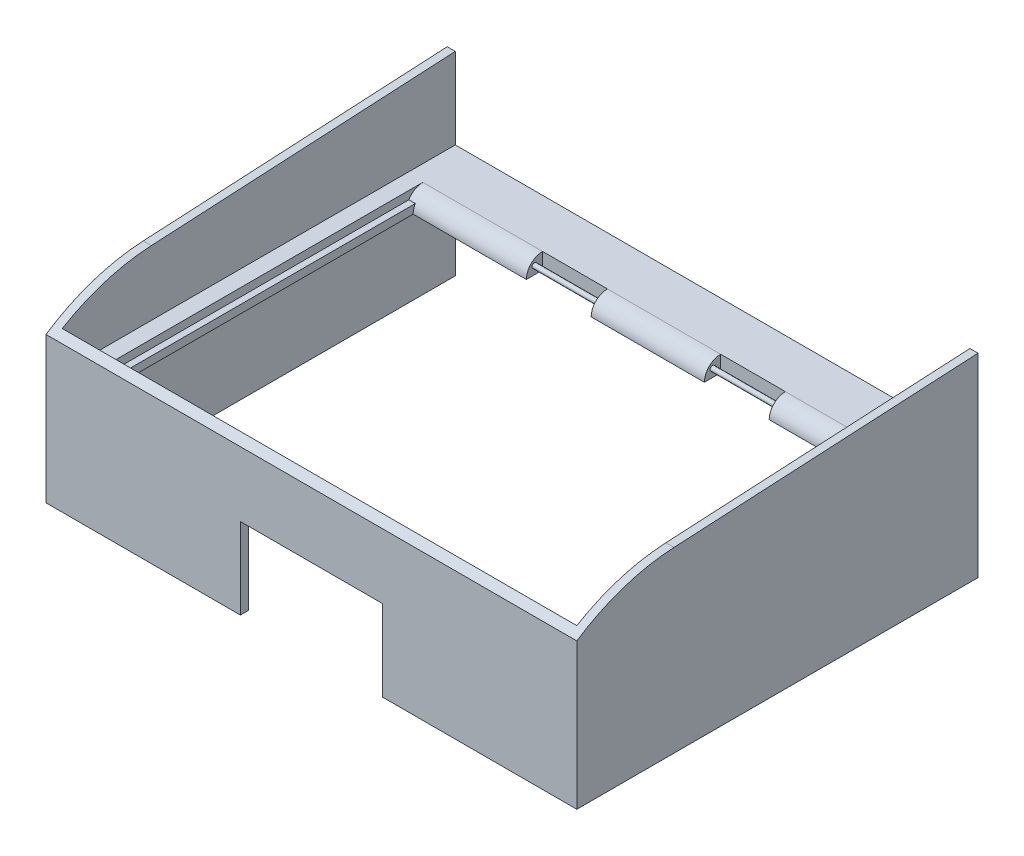
SolidWorks part; units mm, degrees
material "Custom Plastic"
ref_plane "Front Plane" through (0, 0, 0) normal (0, 0, 1) x (1, 0, 0)
ref_plane "Top Plane" through (0, 0, 0) normal (0, 1, 0) x (1, 0, 0)
ref_plane "Right Plane" through (0, 0, 0) normal (1, 0, 0) x (0, 0, -1)
sketch "Sketch1" plane through (0, 0, 0) normal (0, 1, 0) x (1, 0, 0)
  line L15 (-167.513, -142.113) -> (248.567, -142.113)
  line L16 (-167.513, -142.113) -> (-167.513, 172.367)
  line L17 (-167.513, 172.367) -> (248.567, 172.367)
  line L18 (248.567, -142.113) -> (248.567, 172.367)
extrude "Boss-Extrude2" add sketch "Sketch1" along normal blind 152.4
sketch "Sketch2" plane through (0, 152.4, 0) normal (0, 1, 0) x (1, 0, 0)
  line L0 (-167.513, -142.113) -> (248.567, -142.113) construction
  line L1 (-161.163, -135.763) -> (242.217, -135.763)
  line L2 (-161.163, -135.763) -> (-161.163, 172.367)
  line L3 (-161.163, 172.367) -> (242.217, 172.367)
  line L4 (242.217, -135.763) -> (242.217, 172.367)
  line L5 (-167.513, 172.367) -> (-167.513, -142.113) construction
  line L6 (248.567, -142.113) -> (248.567, 172.367) construction
  line L7 (248.567, 172.367) -> (-167.513, 172.367) construction
  dimension "D1" = 6.35
  dimension "D2" = 6.35
  dimension "D3" = 6.35
  dimension "D4" = 0
extrude "Cut-Extrude1" cut sketch "Sketch2" against normal through all
sketch "Sketch3" plane through (248.567, 0, 0) normal (1, 0, 0) x (0, 0, -1)
  line L5 (-142.113, 114.3) -> (-142.113, 152.4)
  line L6 (-142.113, 152.4) -> (-142.113, 0) construction
  line L7 (-142.113, 152.4) -> (172.367, 152.4)
  line L8 (172.367, 152.4) -> (-65.913, 139.7)
  arc A1 (-65.913, 139.7) -> (-142.113, 114.3) centre (-57.8558, -11.4717) ccw
  dimension "D1" = 38.1
  dimension "D2" = 12.7
  dimension "D3" = 76.2
extrude "Cut-Extrude2" cut sketch "Sketch3" against normal through all contours L5 L7 L8 A1
sketch "Sketch4" plane through (0, 0, 142.113) normal (0, 0, 1) x (1, 0, 0)
  line L0 (-167.513, 0) -> (248.567, 0) construction
  line L1 (96.167, 0) -> (-15.113, 0)
  line L2 (96.167, 0) -> (96.167, 63.5)
  line L3 (96.167, 63.5) -> (-15.113, 63.5)
  line L4 (-15.113, 0) -> (-15.113, 63.5)
  line L6 (248.567, 114.3) -> (248.567, 0) construction
  line L7 (-167.513, 114.3) -> (-167.513, 0) construction
  dimension "D1" = 152.4
  dimension "D2" = 152.4
  dimension "D3" = 63.5
extrude "Cut-Extrude3" cut sketch "Sketch4" against normal up to next
sketch "Sketch5" plane through (0, 0, 135.763) normal (0, 0, -1) x (-1, 0, 0)
  line L0 (161.163, 0) -> (161.163, 152.4) construction
  line L1 (-242.217, 88.9) -> (161.163, 88.9)
  line L2 (-242.217, 88.9) -> (-242.217, 76.2)
  line L3 (-242.217, 76.2) -> (161.163, 76.2)
  line L4 (161.163, 88.9) -> (161.163, 76.2)
  line L5 (-96.167, 63.5) -> (15.113, 63.5) construction
  dimension "D1" = 12.7
  dimension "D2" = 12.7
extrude "Boss-Extrude3" add sketch "Sketch5" along normal up to surface (308.13 mm away)
sketch "Sketch6" plane through (0, 88.9, 0) normal (0, 1, 0) x (1, 0, 0)
  line L0 (40.527, -135.763) -> (40.527, 170.2331) construction
  line L1 (242.217, -135.763) -> (-161.163, -135.763) construction
  line L2 (-161.163, 18.302) -> (242.217, 18.302) construction
  line L3 (-161.163, 172.367) -> (-161.163, -135.763) construction
  line L4 (242.217, 172.367) -> (242.217, -135.763) construction
  line L5 (-161.163, 172.367) -> (242.217, 172.367) construction
  line L6 (229.517, -110.363) -> (-148.463, -110.363)
  line L7 (229.517, -110.363) -> (229.517, 121.567)
  line L8 (229.517, 121.567) -> (-148.463, 121.567)
  line L9 (-148.463, -110.363) -> (-148.463, 121.567)
  line L10 (229.517, -110.363) -> (-148.463, 121.567) construction
  line L11 (229.517, 121.567) -> (-148.463, -110.363) construction
  point P10 (40.527, 5.602)
  dimension "D1" = 25.4
  dimension "D2" = 12.7
  dimension "D3" = 50.8
extrude "Cut-Extrude4" cut sketch "Sketch6" against normal blind 6.35
sketch "Sketch7" plane through (0, 82.55, 0) normal (0, 1, 0) x (1, 0, 0)
  line L0 (40.527, -110.363) -> (40.527, 121.567) construction
  line L1 (-148.463, -110.363) -> (229.517, -110.363) construction
  line L2 (229.517, 121.567) -> (-148.463, 121.567) construction
  line L3 (-148.463, 5.602) -> (229.517, 5.602) construction
  line L4 (-148.463, 121.567) -> (-148.463, -110.363) construction
  line L5 (229.517, -110.363) -> (229.517, 121.567) construction
  line L6 (-54.643, 134.267) -> (-3.843, 134.267)
  line L7 (224.437, -105.283) -> (-143.383, -105.283)
  line L8 (224.437, -105.283) -> (224.437, 121.567)
  line L10 (-143.383, -105.283) -> (-143.383, 121.567)
  line L11 (224.437, -105.283) -> (-143.383, 121.567) construction
  line L12 (224.437, 121.567) -> (-143.383, -105.283) construction
  line L13 (-3.843, 134.267) -> (-3.843, 121.567)
  line L14 (-54.643, 134.267) -> (-54.643, 121.567)
  line L15 (-143.383, 121.567) -> (-54.643, 121.567)
  line L16 (224.437, 121.567) -> (135.697, 121.567)
  line L17 (-3.843, 121.567) -> (84.897, 121.567)
  line L18 (40.527, -105.283) -> (-143.383, -105.283) construction
  line L19 (135.697, 134.267) -> (135.697, 121.567)
  line L20 (135.697, 134.267) -> (84.897, 134.267)
  line L21 (84.897, 134.267) -> (84.897, 121.567)
  point P12 (40.527, 8.142)
  point P22 (40.527, 121.567)
  dimension "D1" = 5.08
  dimension "D2" = 5.08
  dimension "D3" = 12.7
  dimension "D4" = 50.8
extrude "Cut-Extrude5" cut sketch "Sketch7" against normal through all both and the other way through all
fillet "Fillet2" radius 12.7 3 edges at (182.607, 88.9, -121.567) (40.527, 88.9, -121.567) (-101.553, 88.9, -121.567)
sketch "Sketch8" plane through (-54.643, 0, 0) normal (1, 0, 0) x (0, 0, -1)
  line L0 (134.267, 82.55) -> (88.213, 82.55) construction
  line L1 (134.267, 76.2) -> (134.267, 88.9) construction
  line L2 (127.917, 76.2) -> (127.917, 94.6214) construction
  line L3 (134.267, 76.2) -> (121.567, 76.2) construction
  circle A0 centre (127.917, 82.55) radius 1.905
  dimension "D1" = 3.81
extrude "Boss-Extrude4" add sketch "Sketch8" along normal up to surface (190.34 mm away) up to face at (135.697, 81.3101, -129.1569)
